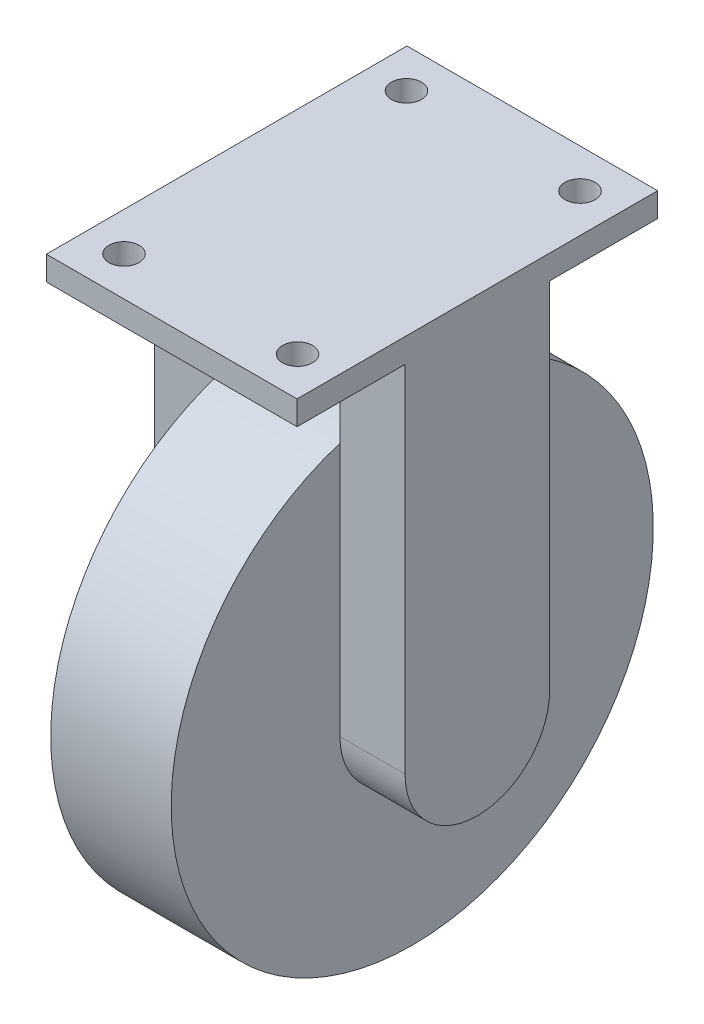
SolidWorks part; units mm, degrees
ref_plane "Front Plane" through (0, 0, 0) normal (0, 0, 1) x (1, 0, 0)
ref_plane "Top Plane" through (0, 0, 0) normal (0, 1, 0) x (1, 0, 0)
ref_plane "Right Plane" through (0, 0, 0) normal (1, 0, 0) x (0, 0, -1)
sketch "Sketch1" plane through (0, 0, 0) normal (1, 0, 0) x (0, 0, -1)
  circle A0 centre (0, 0) radius 63.5
  dimension "D1" = 127
extrude "Boss-Extrude1" add sketch "Sketch1" along normal mid plane 31.75
sketch "Sketch2" plane through (0, 0, 0) normal (0, 1, 0) x (1, 0, 0)
  line L1 (33.02, -47.498) -> (-33.02, -47.498)
  line L2 (33.02, -47.498) -> (33.02, 47.498)
  line L3 (33.02, 47.498) -> (-33.02, 47.498)
  line L4 (-33.02, -47.498) -> (-33.02, 47.498)
  line L5 (0, 47.498) -> (0, -47.498) construction
  line L6 (33.02, 0) -> (-33.02, 0) construction
  circle A0 centre (-22.86, 37.211) radius 3.9688
  circle A1 centre (22.86, 37.211) radius 3.9688
  circle A2 centre (22.86, -37.211) radius 3.9688
  circle A3 centre (-22.86, -37.211) radius 3.9688
  point P0 (0, 0)
  point P12 (0, 0)
  point P13 (0, 0)
  point P14 (0, 0)
  point P15 (0, 0)
  point P16 (-24.2598, 43.0386)
  point P17 (-19.2671, 34.9734)
  dimension "D5" = 7.9375
  dimension "D1" = 45.72
  dimension "D2" = 74.422
  dimension "D3" = 94.996
  dimension "D4" = 66.04
extrude "Boss-Extrude2" add sketch "Sketch2" against normal blind 6.35 from offset 93.472 separate body
sketch "Sketch3" plane through (0, 87.122, 0) normal (0, -1, 0) x (1, 0, 0)
  line L0 (-33.02, -47.498) -> (-33.02, 47.498) construction
  line L1 (-33.02, 19.05) -> (-15.875, 19.05)
  line L2 (-33.02, 19.05) -> (-33.02, -19.05)
  line L3 (-33.02, -19.05) -> (-15.875, -19.05)
  line L4 (-15.875, 19.05) -> (-15.875, -19.05)
  line L5 (-15.875, 63.5) -> (-15.875, -63.5) construction
  line L6 (15.875, -63.5) -> (15.875, 63.5) construction
  line L7 (15.875, 19.05) -> (33.02, 19.05)
  line L8 (15.875, 19.05) -> (15.875, -19.05)
  line L9 (15.875, -19.05) -> (33.02, -19.05)
  line L10 (33.02, 19.05) -> (33.02, -19.05)
  line L11 (33.02, 47.498) -> (33.02, -47.498) construction
  point P16 (-15.875, 0)
  dimension "D1" = 38.1
extrude "Boss-Extrude3" add sketch "Sketch3" along normal blind 112.522
fillet "Fillet1" radius 19.05 4 edges at (-24.4475, -25.4, -19.05) (-24.4475, -25.4, 19.05) (24.4475, -25.4, 19.05) (24.4475, -25.4, -19.05)
